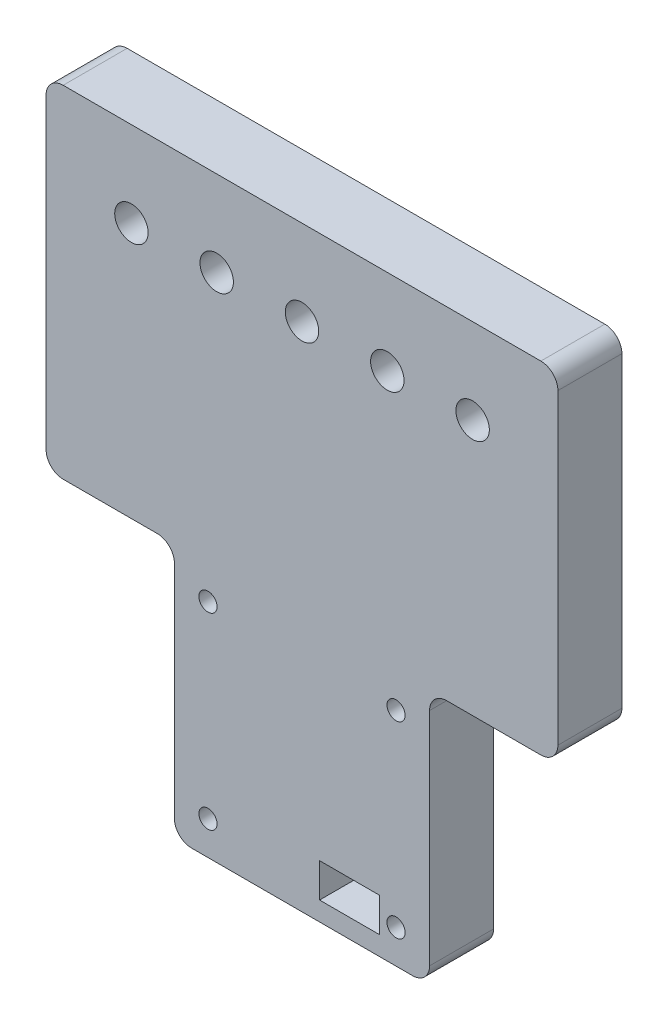
SolidWorks part; units mm, degrees
ref_plane "Front Plane" through (0, 0, 0) normal (1, 0, 0) x (0, 1, 0)
ref_plane "Top Plane" through (0, 0, 0) normal (0, 0, 1) x (0, 1, 0)
ref_plane "Right Plane" through (0, 0, 0) normal (0, 1, 0) x (-1, 0, 0)
sketch "Sketch1" plane through (0, 0, 0) normal (0, 0, 1) x (0, 1, 0)
  line L1 (-14, -14) -> (14, -14) construction
  line L2 (-14, -14) -> (-14, 14) construction
  line L3 (-14, 14) -> (14, 14) construction
  line L4 (14, -14) -> (14, 14) construction
  line L5 (-14, -14) -> (14, 14) construction
  line L6 (-14, 14) -> (14, -14) construction
  line L7 (-19, -19) -> (19, -19)
  line L8 (-19, -19) -> (-19, 19)
  line L9 (-19, 19) -> (19, 19)
  line L10 (19, -19) -> (19, 19)
  line L11 (-19, -19) -> (19, 19) construction
  line L12 (-19, 19) -> (19, -19) construction
  point P0 (0, 0)
  point P7 (0, 0)
  dimension "D1" = 28
  dimension "D2" = 28
  dimension "D3" = 38
  dimension "D4" = 38
extrude "Boss-Extrude1" add sketch "Sketch1" along normal blind 9.525
sketch "Sketch2" plane through (0, 0, 9.525) normal (0, 0, 1) x (1, 0, 0)
  point P0 (-14, -14)
  point P2 (14, -14)
  point P4 (14, 14)
  point P6 (-14, 14)
hole_wizard "#36 (0.1065) Diameter Hole2" positions "Sketch2" profile "Sketch4" hole size "#36" standard "ANSI Inch" end condition through all
sketch "Sketch4" plane through (-14, -14, 9.525) normal (1, 0, 0) x (0, -1, 0)
  line L0 (0, 0) -> (0, 9.525)
  line L1 (0, 9.525) -> (1.3525, 9.525)
  line L2 (1.3525, 9.525) -> (1.3525, 0)
  line L5 (1.3525, 0) -> (0, 0)
  line L11 (0, -6.35) -> (0, 107.95) construction
  dimension "Thru Hole Dia." = 2.7051
  dimension "Thru Hole Depth" = 9.525
sketch "Sketch7" plane through (0, 0, 0) normal (0, 0, -1) x (1, 0, 0)
  line L1 (2.615, 11.09) -> (11.505, 11.09)
  line L2 (2.615, 11.09) -> (2.615, 16.17)
  line L3 (2.615, 16.17) -> (11.505, 16.17)
  line L4 (11.505, 11.09) -> (11.505, 16.17)
  line L5 (2.615, 11.09) -> (11.505, 16.17) construction
  line L6 (2.615, 16.17) -> (11.505, 11.09) construction
  circle A0 centre (14, 14) radius 1.3525 construction
  point P0 (7.06, 13.63)
  dimension "D1" = 8.89
  dimension "D2" = 5.08
  dimension "D3" = 0.37
  dimension "D4" = 6.94
extrude "Cut-Extrude1" cut sketch "Sketch7" against normal through all
sketch "Sketch8" plane through (0, 19, 0) normal (0, 1, 0) x (-1, 0, 0)
  line L1 (38.1, 9.525) -> (-38.1, 9.525)
  line L2 (38.1, 9.525) -> (38.1, 0)
  line L3 (38.1, 0) -> (-38.1, 0)
  line L4 (-38.1, 9.525) -> (-38.1, 0)
  point P8 (0, 0)
  dimension "D1" = 76.2
extrude "Boss-Extrude2" add sketch "Sketch8" along normal blind 50.8
sketch "Sketch9" plane through (0, 0, 0) normal (0, 0, -1) x (1, 0, 0)
  line L1 (-38.1, -69.8) -> (-38.1, -19) construction
  line L2 (38.1, -69.8) -> (-38.1, -69.8) construction
  point P0 (-25.4, -57.1)
  point P8 (-12.7, -57.1)
  point P9 (0, -57.1)
  point P10 (12.7, -57.1)
  point P11 (25.4, -57.1)
  dimension "D1" = 12.7
  dimension "D2" = 12.7
  dimension "D4" = 12.7
  dimension "D3" = 5
hole_wizard "#9 (0.196) Diameter Hole1" positions "Sketch9" profile "Sketch10" hole size "#9" standard "ANSI Inch" end condition through all
sketch "Sketch10" plane through (-25.4, 57.1, 0) normal (1, 0, 0) x (0, 1, 0)
  line L0 (0, 0) -> (0, 9.525)
  line L1 (0, 9.525) -> (2.4892, 9.525)
  line L2 (2.4892, 9.525) -> (2.4892, 0)
  line L5 (2.4892, 0) -> (0, 0)
  line L11 (0, -6.35) -> (0, 107.95) construction
  dimension "Thru Hole Dia." = 4.9784
  dimension "Thru Hole Depth" = 9.525
fillet "Fillet1" radius 2.54 8 edges at (-38.1, 69.8, 4.7625) (38.1, 69.8, 4.7625) (38.1, 19, 4.7625) (19, 19, 4.7625) (19, -19, 4.7625) (-19, -19, 4.7625) (-19, 19, 4.7625) (-38.1, 19, 4.7625)
